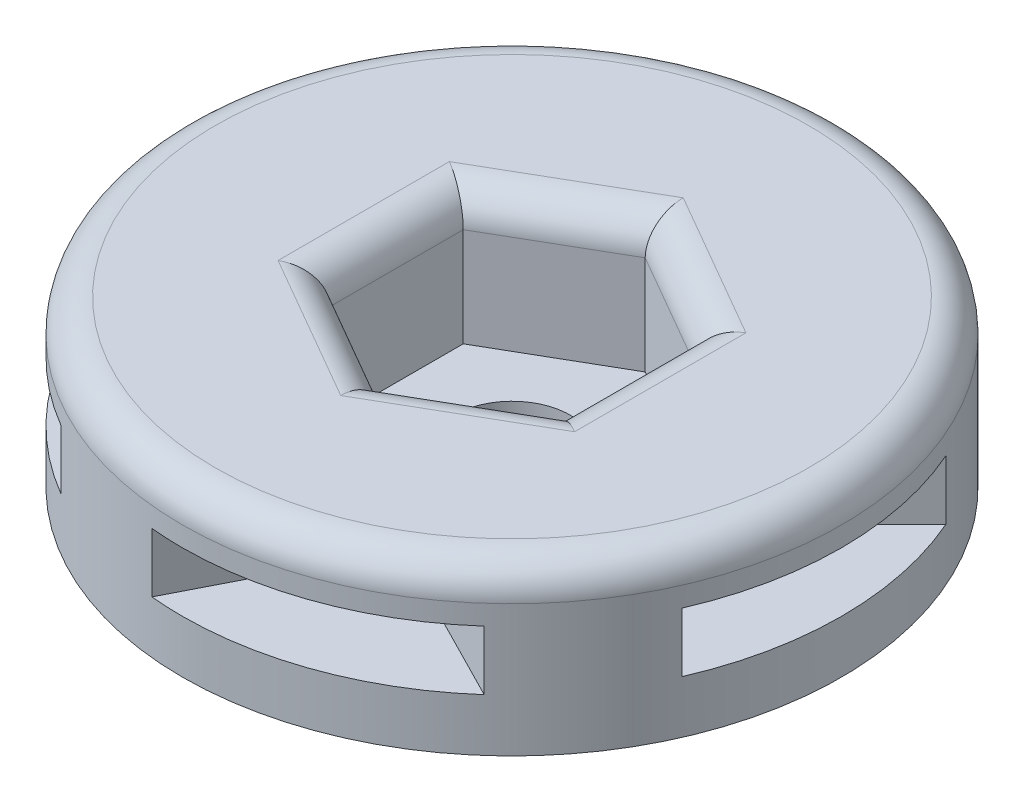
SolidWorks part; units mm, degrees
ref_plane "Front Plane" through (0, 0, 0) normal (0, 0, 1) x (1, 0, 0)
ref_plane "Top Plane" through (0, 0, 0) normal (0, 1, 0) x (1, 0, 0)
ref_plane "Right Plane" through (0, 0, 0) normal (1, 0, 0) x (0, 0, -1)
sketch "Sketch2" plane through (0, 0, 0) normal (0, 1, 0) x (1, 0, 0)
  line L1 (0, 5.1326) -> (-4.445, 2.5663)
  line L2 (-4.445, 2.5663) -> (-4.445, -2.5663)
  line L3 (-4.445, -2.5663) -> (0, -5.1326)
  line L4 (0, -5.1326) -> (4.445, -2.5663)
  line L5 (4.445, -2.5663) -> (4.445, 2.5663)
  line L6 (4.445, 2.5663) -> (0, 5.1326)
  circle A0 centre (0, 0) radius 12.7
  circle A1 centre (0, 0) radius 4.445 construction
  dimension "D1" = 25.4
  dimension "D2" = 8.89
extrude "Boss-Extrude1" add sketch "Sketch2" along normal mid plane 6.35
sketch "Sketch3" plane through (0, 0, 0) normal (0, 1, 0) x (1, 0, 0)
  line L0 (11.6397, 5.08) -> (11.6397, -5.08) construction
  line L1 (11.6397, 5.08) -> (7.8297, 1.27)
  line L2 (7.8297, 1.27) -> (7.8297, -1.27)
  line L3 (7.8297, -1.27) -> (11.6397, -5.08)
  circle A0 centre (0, 0) radius 12.7 construction
  circle A2 centre (0, 0) radius 12.7
  arc A3 (11.6397, -5.08) -> (11.6397, 5.08) centre (0, 0) ccw
  dimension "D1" = 10.16
  dimension "D2" = 45
  dimension "D3" = 3.81
  dimension "D4" = 0
extrude "Cut-Extrude1" cut sketch "Sketch3" against normal mid plane 2.286
ref_axis "Axis1" through (0, -3.4925, 0) along (0, 1, 0)
pattern_circular "CirPattern1" count 5 over 360 about axis through (0, -3.4925, 0) along (0, 1, 0) of "Cut-Extrude1"
fillet "Fillet1" radius 1.27 7 edges at (0, 3.175, 12.7) (-4.445, 3.175, 0) (-2.2225, 3.175, 3.8495) (2.2225, 3.175, 3.8495) (4.445, 3.175, 0) (2.2225, 3.175, -3.8495) (-2.2225, 3.175, -3.8495)
sketch "Sketch4" plane through (0, -3.175, 0) normal (0, -1, 0) x (1, 0, 0)
  line L0 (4.445, 2.5663) -> (4.445, -2.5663) construction
  line L1 (0, 5.1326) -> (4.445, 2.5663) construction
  line L2 (4.445, -2.5663) -> (0, -5.1326) construction
  line L3 (0, -5.1326) -> (-4.445, -2.5663) construction
  line L4 (-4.445, 2.5663) -> (0, 5.1326) construction
  line L5 (-4.445, -2.5663) -> (-4.445, 2.5663) construction
  line L6 (4.445, 2.5663) -> (4.445, -2.5663)
  line L7 (0, 5.1326) -> (4.445, 2.5663)
  line L8 (4.445, -2.5663) -> (0, -5.1326)
  line L9 (0, -5.1326) -> (-4.445, -2.5663)
  line L10 (-4.445, 2.5663) -> (0, 5.1326)
  line L11 (-4.445, -2.5663) -> (-4.445, 2.5663)
extrude "Boss-Extrude2" add sketch "Sketch4" against normal blind 1.27
hole_wizard "M4 Clearance Hole1" positions "Sketch5" profile "Sketch7" hole size "M4" standard "ANSI Metric" end condition through all
sketch "Sketch5" plane through (0, -1.905, 0) normal (0, 1, 0) x (1, 0, 0)
  point P0 (0, 0)
sketch "Sketch7" plane through (0, -1.905, 0) normal (1, 0, 0) x (0, 0, 1)
  line L0 (0, 0) -> (0, 1.27)
  line L1 (0, 1.27) -> (2.25, 1.27)
  line L2 (2.25, 1.27) -> (2.25, 0)
  line L5 (2.25, 0) -> (0, 0)
  line L11 (0, -6.35) -> (0, 107.95) construction
  dimension "Thru Hole Dia." = 4.5
  dimension "Thru Hole Depth" = 1.27
